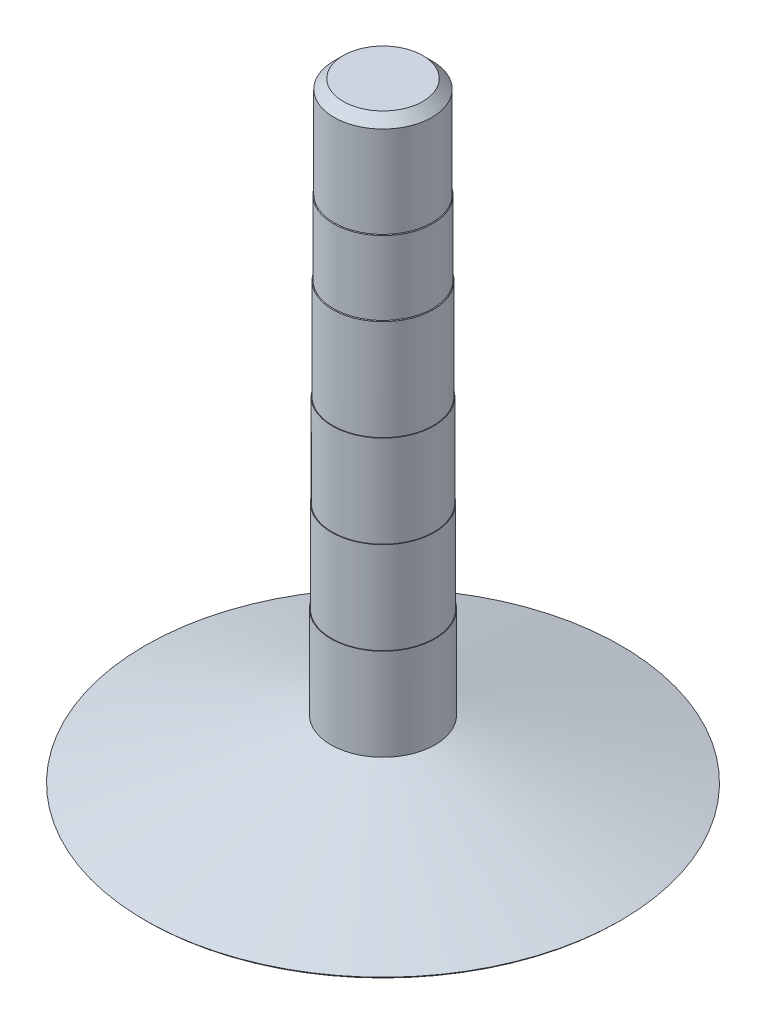
SolidWorks part; units mm, degrees
ref_plane "Front Plane" through (0, 0, 0) normal (0, 0, 1) x (1, 0, 0)
ref_plane "Top Plane" through (0, 0, 0) normal (0, 1, 0) x (1, 0, 0)
ref_plane "Right Plane" through (0, 0, 0) normal (1, 0, 0) x (0, 0, -1)
sketch "Sketch1" plane through (0, 0, 0) normal (0, 0, 1) x (1, 0, 0)
  line L0 (0, 25) -> (0, -25)
  line L3 (-4.1, 10) -> (-4.05, 10)
  line L4 (-4.05, 10) -> (-4.05, 17.5)
  line L5 (-4.05, 17.5) -> (-4, 17.5)
  line L6 (-4, 17.5) -> (-4, 25)
  line L7 (-4, 25) -> (0, 25)
  line L8 (0, 37.2712) -> (0, -38.1367) construction
  line L9 (-4.1, 10) -> (-4.1, 2.5)
  line L10 (-4.25, -20) -> (-20, -25)
  line L11 (0, -25) -> (-20, -25)
  line L12 (-4.1, 2.5) -> (-4.15, 2.5)
  line L13 (-4.15, 2.5) -> (-4.15, -5)
  line L14 (-4.15, -5) -> (-4.2, -5)
  line L15 (-4.2, -5) -> (-4.2, -12.5)
  line L16 (-4.2, -12.5) -> (-4.25, -12.5)
  line L17 (-4.25, -12.5) -> (-4.25, -20)
  point P19 (0, 0)
  dimension "D1" = 8.1
  dimension "D2" = 8
  dimension "D3" = 7.5
  dimension "D4" = 7.5
  dimension "D5" = 50
  dimension "D6" = 5
  dimension "D7" = 8.2
  dimension "D8" = 20
  dimension "D9" = 8.3
  dimension "D10" = 8.4
  dimension "D11" = 4.25
revolve "Revolve1" add sketch "Sketch1" angle 360 about L8 region at (-3.2578, -3.9879, 0)
chamfer "Chamfer1" distance 0.75 angle 45 4 edges at (-4, 25, 0) (-4.05, 17.5, 0) (-4.05, 10, 0) (-20, -25, 0) first distance on face at (-4, 25, 0) first distance on face at (-4.05, 17.5, 0) first distance on face at (-4.05, 10, 0) first distance on face at (-20, -25, 0)
